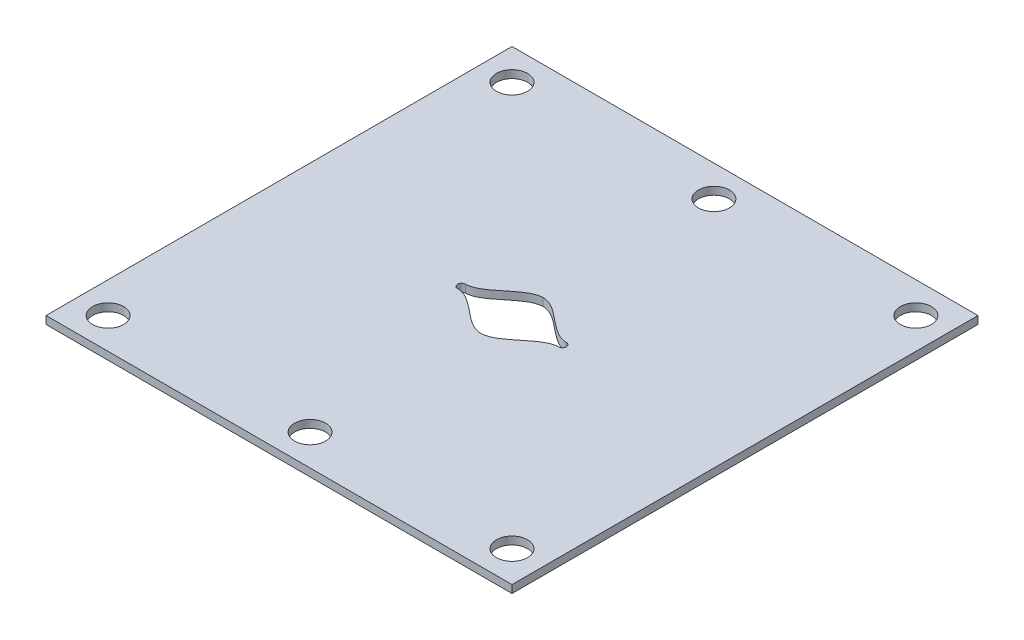
SolidWorks part; units mm, degrees
ref_plane "Front Plane" through (0, 0, 0) normal (0, 0, 1) x (1, 0, 0)
ref_plane "Top Plane" through (0, 0, 0) normal (0, 1, 0) x (1, 0, 0)
ref_plane "Right Plane" through (0, 0, 0) normal (1, 0, 0) x (0, 0, -1)
sketch "Sketch1" plane through (0, 0, 0) normal (0, 1, 0) x (1, 0, 0)
  line L1 (30, -30) -> (-30, -30)
  line L2 (30, -30) -> (30, 30)
  line L3 (30, 30) -> (-30, 30)
  line L4 (-30, -30) -> (-30, 30)
  line L5 (30, -30) -> (-30, 30) construction
  line L6 (30, 30) -> (-30, -30) construction
  point P0 (0, 0)
  dimension "D1" = 60
  dimension "D2" = 60
extrude "Boss-Extrude1" add sketch "Sketch1" along normal blind 1
hole_wizard "Ø4.0 (4) Diameter Hole1" positions "Sketch13" profile "Sketch12" hole size "Ø4.0" standard "ANSI Metric" end condition up to next
sketch "Sketch13" plane through (0, 1, 0) normal (0, 1, 0) x (1, 0, 0)
  line L0 (0, 30) -> (0, -30) construction
  line L1 (30, 30) -> (-30, 30) construction
  line L2 (-30, -30) -> (30, -30) construction
  line L4 (-30, 0) -> (30, 0) construction
  line L5 (-30, 30) -> (-30, -30) construction
  line L6 (30, -30) -> (30, 30) construction
  point P17 (26, 26)
  point P24 (0, 26)
  point P27 (-26, 26)
  point P28 (0, -26)
  point P29 (26, -26)
  point P30 (-26, -26)
  dimension "D1" = 4
  dimension "D2" = 4
sketch "Sketch12" plane through (26, 1, -26) normal (1, 0, 0) x (0, 0, 1)
  line L0 (0, 0) -> (0, 1)
  line L1 (0, 1) -> (2, 1)
  line L2 (2, 1) -> (2, 0)
  line L5 (2, 0) -> (0, 0)
  line L11 (0, -6.35) -> (0, 107.95) construction
  dimension "Thru Hole Dia." = 4
  dimension "Thru Hole Depth" = 1
sketch "Sketch14" plane through (0, 1, 0) normal (0, 1, 0) x (1, 0, 0)
  line L3 (7.5, -5) -> (-7.5, -5)
  line L6 (7.5, -5) -> (7.5, 5)
  line L7 (7.5, 5) -> (-7.5, 5)
  line L8 (-7.5, -5) -> (-7.5, 5)
  line L9 (7.5, -5) -> (-7.5, 5) construction
  line L10 (7.5, 5) -> (-7.5, -5) construction
  point P0 (0, 0)
  dimension "D1" = 15
  dimension "D2" = 10
extrude "Chip Cutout" [suppressed] cut sketch "Sketch14" against normal blind 10
sketch "Sketch19" plane through (0, 1, 0) normal (0, 1, 0) x (1, 0, 0)
  line L0 (0, 30) -> (0, -30) construction
  line L1 (30, 30) -> (-30, 30) construction
  line L2 (-30, -30) -> (30, -30) construction
  line L3 (-30, 0) -> (30, 0) construction
  line L4 (-30, 30) -> (-30, -30) construction
  line L5 (30, -30) -> (30, 30) construction
  arc A0 (-6.5, -0.5) -> (-6.5, 0.5) centre (-6.5, 0) cw
  arc A1 (6.5, -0.5) -> (6.5, 0.5) centre (6.5, 0) ccw
  spline S0 degree 3 poles (-7.15, 0.612) (-4.55, -0.312) (-1.95, 4.812) (0.65, 3.888) knots 0 0 0 0 1 1 1 1 construction
  spline S1 degree 3 poles (-6.5, 0.5) (-4.3333, 0.5) (-2.1667, 4) (0, 4) knots 0.083333 0.083333 0.083333 0.083333 0.916667 0.916667 0.916667 0.916667
  spline S2 degree 3 poles (6.5, 0.5) (4.3333, 0.5) (2.1667, 4) (0, 4) knots 0.083333 0.083333 0.083333 0.083333 0.916667 0.916667 0.916667 0.916667
  spline S3 degree 3 poles (6.5, -0.5) (4.3333, -0.5) (2.1667, -4) (0, -4) knots 0.083333 0.083333 0.083333 0.083333 0.916667 0.916667 0.916667 0.916667
  spline S4 degree 3 poles (-6.5, -0.5) (-4.3333, -0.5) (-2.1667, -4) (0, -4) knots 0.083333 0.083333 0.083333 0.083333 0.916667 0.916667 0.916667 0.916667
extrude "iCell" cut sketch "Sketch19" against normal blind 10
